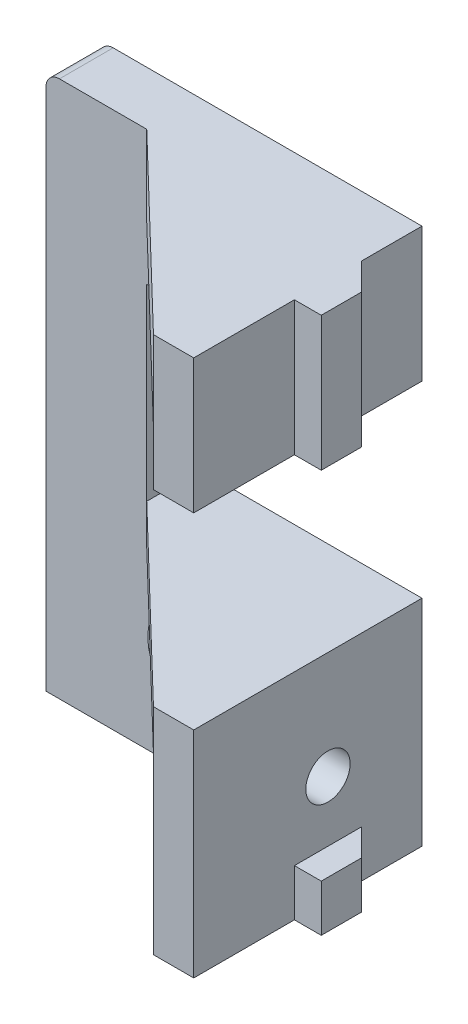
SolidWorks part; units mm, degrees
ref_plane "Front Plane" through (0, 0, 0) normal (0, 0, 1) x (1, 0, 0)
ref_plane "Top Plane" through (0, 0, 0) normal (0, 1, 0) x (1, 0, 0)
ref_plane "Right Plane" through (0, 0, 0) normal (1, 0, 0) x (0, 0, -1)
sketch "Sketch1" plane through (0, 0, 0) normal (0, 0, 1) x (1, 0, 0)
  line L1 (-26.7581, 33.2419) -> (-2.7581, 33.2419)
  line L2 (-26.7581, 33.2419) -> (-26.7581, -6.7581)
  line L3 (-26.7581, -6.7581) -> (-2.7581, -6.7581)
  line L4 (-2.7581, 33.2419) -> (-2.7581, -6.7581)
  dimension "D1" = 40
  dimension "D2" = 24
extrude "Boss-Extrude1" add sketch "Sketch1" along normal blind 4
fillet "Fillet1" radius 1 1 edges at (-26.7581, 33.2419, 2)
sketch "Sketch3" plane through (0, 0, 0) normal (0, 0, -1) x (-1, 0, 0)
  line L0 (2.7581, -6.7581) -> (2.7581, 33.2419) construction
  line L1 (2.7581, 9.2419) -> (19.2581, 9.2419)
  line L2 (2.7581, 9.2419) -> (2.7581, 23.2419)
  line L3 (2.7581, 23.2419) -> (19.2581, 23.2419)
  line L4 (19.2581, 9.2419) -> (19.2581, 23.2419)
  line L5 (26.7581, -6.7581) -> (2.7581, -6.7581) construction
  dimension "D1" = 14
  dimension "D2" = 16.5
  dimension "D3" = 16
extrude "Cut-Extrude2" cut sketch "Sketch3" against normal through all both and the other way through all
sketch "Sketch5" plane through (0, 0, 4) normal (0, 0, 1) x (1, 0, 0)
  line L0 (-26.7581, -6.7581) -> (-2.7581, -6.7581) construction
  line L1 (-2.7581, 9.2419) -> (-5.7581, 9.2419)
  line L2 (-2.7581, 9.2419) -> (-2.7581, -6.7581)
  line L3 (-2.7581, -6.7581) -> (-5.7581, -6.7581)
  line L4 (-5.7581, 9.2419) -> (-5.7581, -6.7581)
  dimension "D1" = 3
extrude "Boss-Extrude2" add sketch "Sketch5" along normal blind 13
sketch "Sketch6" plane through (0, -6.7581, 0) normal (0, -1, 0) x (1, 0, 0)
  line L0 (-5.7581, 17) -> (-16.6664, 4)
  line L1 (-26.7581, 4) -> (-5.7581, 4) construction
  line L2 (-16.6664, 4) -> (-5.7581, 4)
  line L3 (-5.7581, 4) -> (-5.7581, 17)
extrude "Boss-Extrude3" add sketch "Sketch6" against normal blind 3
sketch "Sketch7" plane through (0, 9.2419, 0) normal (0, 1, 0) x (1, 0, 0)
  line L0 (-5.7581, -17) -> (-19.2581, -4)
  line L1 (-19.2581, -4) -> (-5.7581, -4)
  line L2 (-5.7581, -4) -> (-5.7581, -17)
extrude "Boss-Extrude4" add sketch "Sketch7" against normal blind 3
sketch "Sketch8" plane through (-5.7581, 0, 0) normal (-1, 0, 0) x (0, 0, 1)
  line L0 (17, 6.2419) -> (17, -3.7581) construction
  line L1 (17, -6.7581) -> (4, -6.7581) construction
  circle A0 centre (7, 1.2419) radius 1.65
  dimension "D1" = 3.3
  dimension "D2" = 10
  dimension "D3" = 8
extrude "Cut-Extrude4" cut sketch "Sketch8" against normal blind 3
sketch "Sketch9" plane through (0, 0, 4) normal (0, 0, 1) x (1, 0, 0)
  line L0 (-19.2581, 23.2419) -> (-2.7581, 23.2419) construction
  line L1 (-2.7581, 33.2419) -> (-5.7581, 33.2419)
  line L2 (-2.7581, 33.2419) -> (-2.7581, 23.2419)
  line L3 (-2.7581, 23.2419) -> (-5.7581, 23.2419)
  line L4 (-5.7581, 33.2419) -> (-5.7581, 23.2419)
  dimension "D1" = 3
extrude "Boss-Extrude5" add sketch "Sketch9" along normal blind 13
sketch "Sketch10" plane through (0, 33.2419, 0) normal (0, 1, 0) x (1, 0, 0)
  line L0 (-5.7581, -17) -> (-19.2581, -4)
  line L1 (-19.2581, -4) -> (-5.7581, -4)
  line L2 (-5.7581, -4) -> (-5.7581, -17)
extrude "Boss-Extrude6" add sketch "Sketch10" against normal blind 6
sketch "Sketch11" plane through (-2.7581, 0, 0) normal (1, 0, 0) x (0, 0, -1)
  line L0 (-17, 33.2419) -> (0, 33.2419) construction
  line L1 (-9.5, 33.2419) -> (-4.5, 33.2419)
  line L2 (-9.5, 33.2419) -> (-9.5, 23.2419)
  line L3 (-9.5, 23.2419) -> (-4.5, 23.2419)
  line L4 (-4.5, 33.2419) -> (-4.5, 23.2419)
  line L5 (-17, 23.2419) -> (0, 23.2419) construction
  line L6 (-17, 23.2419) -> (-17, 33.2419) construction
  dimension "D1" = 5
  dimension "D2" = 7.5
extrude "Boss-Extrude7" add sketch "Sketch11" along normal blind 2
chamfer "Chamfer1" distance 2 angle 45 1 edges at (-0.7581, 28.2419, 4.5)
sketch "Sketch12" plane through (0, 0, 0) normal (0, 0, -1) x (-1, 0, 0)
  line L0 (26.7581, -6.7581) -> (2.7581, -6.7581) construction
  line L5 (2.7581, -6.7581) -> (2.7581, 9.2419) construction
  circle A0 centre (14.7581, 1.2419) radius 3.1
  dimension "D1" = 6.2
  dimension "D2" = 8
  dimension "D4" = 12
extrude "Cut-Extrude5" cut sketch "Sketch12" against normal blind 3.1
sketch "Sketch17" plane through (0, 0, 4) normal (0, 0, 1) x (1, 0, 0)
  circle A1 centre (-14.7581, 1.2419) radius 4
  dimension "D1" = 8
extrude "Boss-Extrude8" add sketch "Sketch17" along normal blind 1
fillet "Fillet3" radius 1 1 edges at (-10.7581, 1.2419, 5)
sketch "Sketch21" plane through (0, 0, 0) normal (0, 0, -1) x (-1, 0, 0)
  circle A0 centre (14.7581, 1.2419) radius 2.25
  dimension "D1" = 4.5
extrude "Boss-Extrude11" add sketch "Sketch21" against normal blind 2.9 separate body contours A0
sketch "Sketch23" plane through (-2.7581, 0, 0) normal (1, 0, 0) x (0, 0, -1)
  line L0 (-17, -6.7581) -> (0, -6.7581) construction
  line L1 (-9.5, -6.7581) -> (-4.5, -6.7581)
  line L2 (-9.5, -6.7581) -> (-9.5, -3.2581)
  line L3 (-9.5, -3.2581) -> (-4.5, -3.2581)
  line L4 (-4.5, -6.7581) -> (-4.5, -3.2581)
  dimension "D1" = 3.5
extrude "Boss-Extrude12" add sketch "Sketch23" along normal blind 2
chamfer "Chamfer2" distance 2 angle 45 1 edges at (-0.7581, -5.0081, 4.5)
fillet "Fillet6" radius 0.5 1 edges at (-17.8581, 1.2419, 0)
sketch "Sketch24" plane through (0, 0, 0) normal (0, 0, -1) x (-1, 0, 0)
  line L0 (2.7581, 23.2419) -> (19.2581, 23.2419) construction
  line L1 (2.7581, 23.2419) -> (2.7581, 33.2419) construction
  circle A0 centre (10.5081, 25.7419) radius 1.35
  dimension "D1" = 2.7
  dimension "D2" = 2.5
  dimension "D3" = 7.75
extrude "Cut-Extrude6" cut sketch "Sketch24" against normal blind 2.7 contours A0
fillet "Fillet7" radius 0.5 1 edges at (-11.8581, 25.7419, 0)
